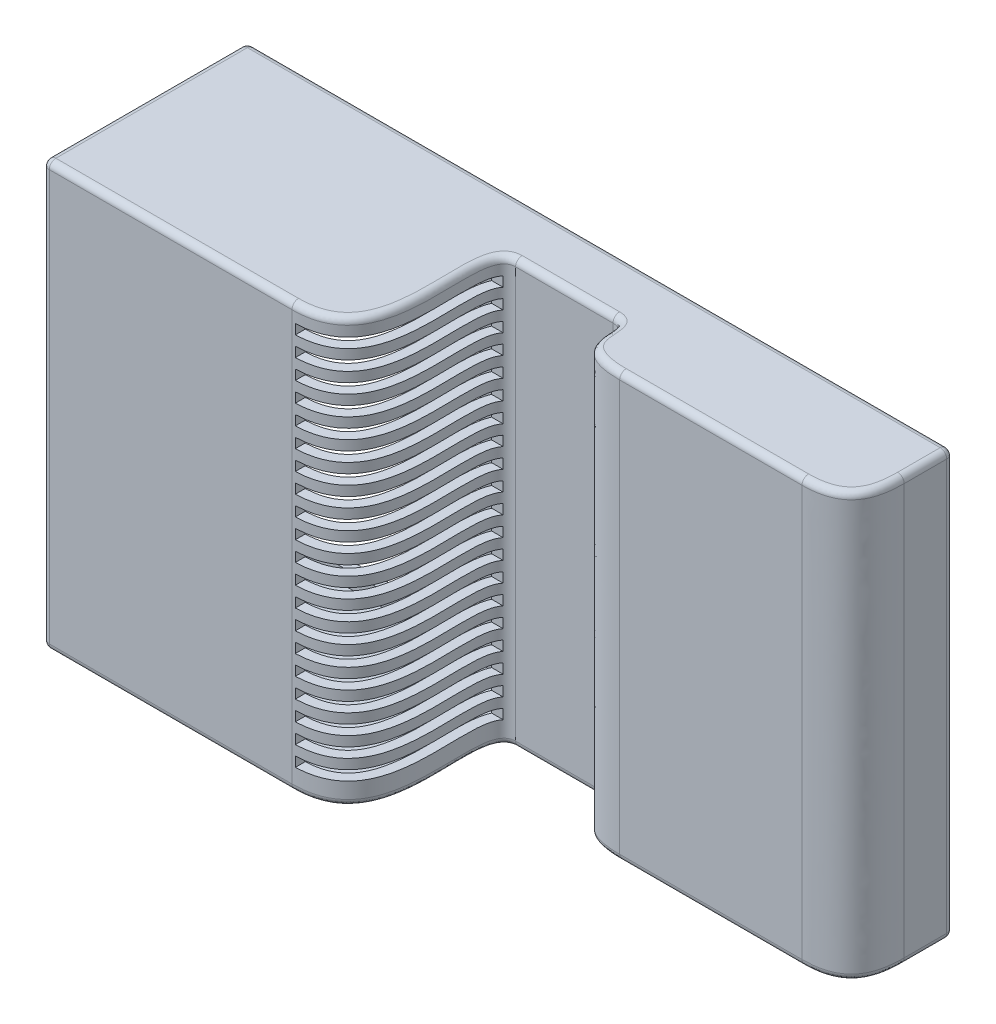
SolidWorks part; units mm, degrees
note: The reader was unsure of these and kept them because the rebuilt part matched: shared geometry of "Sketch1<3>", "Sketch1<4>", "curve_sketch<3>".
ref_plane "Front Plane" through (0, 0, 0) normal (0, 0, 1) x (1, 0, 0)
ref_plane "Top Plane" through (0, 0, 0) normal (0, 1, 0) x (1, 0, 0)
ref_plane "Right Plane" through (0, 0, 0) normal (1, 0, 0) x (0, 0, -1)
sketch "Sketch1" plane through (0, 0, 0) normal (0, 0, 1) x (1, 0, 0)
  line L0 (-14.745, 28.505) -> (-14.745, -28.505)
  line L1 (-13.745, 27.505) -> (13.745, 27.505) construction
  line L2 (-13.745, 27.505) -> (-13.745, -27.505) construction
  line L3 (-13.745, -27.505) -> (13.745, -27.505) construction
  line L4 (13.745, 27.505) -> (13.745, -27.505) construction
  line L5 (-14.745, -28.505) -> (14.745, -28.505)
  line L6 (14.745, 28.505) -> (14.745, -28.505)
  line L7 (-14.745, 28.505) -> (14.745, 28.505)
  line L13 (83.735, 30.745) -> (-20.6993, 30.745)
  line L14 (83.735, 30.745) -> (83.735, -30.755)
  line L15 (83.735, -30.755) -> (-20.6993, -30.755)
  line L16 (-20.6993, 30.745) -> (-20.6993, -30.755)
  line L20 (85.235, 32.245) -> (-22.1993, 32.245)
  line L21 (-22.1993, 32.245) -> (-22.1993, -32.255)
  line L22 (85.235, -32.255) -> (-22.1993, -32.255)
  line L23 (85.235, 32.245) -> (85.235, -32.255)
  line L25 (23.925, 19.36) -> (23.925, -19.36)
  line L26 (24.425, 18.86) -> (76.035, 18.86) construction
  line L27 (24.425, 18.86) -> (24.425, -18.86) construction
  line L28 (24.425, -18.86) -> (76.035, -18.86) construction
  line L29 (76.035, 18.86) -> (76.035, -18.86) construction
  line L30 (23.925, -19.36) -> (76.535, -19.36)
  line L31 (76.535, 19.36) -> (76.535, -19.36)
  line L32 (23.925, 19.36) -> (76.535, 19.36)
  dimension "D3" = 0.5
  dimension "D1" = 1
  dimension "D7" = 1.5
extrude "top" add sketch "Sketch1" against normal blind 1.5 contours L16 L13 L14 L15 L0 L7 L6 L5 | L20 L23 L22 L21 L13 L16 L15 L14
extrude "walls" add sketch "Sketch1<3>" along normal offset from surface (29.6426 mm away) 1 contours L23 L20 L21 L22 L16 L13 L14 L15
sketch "Sketch1<3>" plane through (0, 0, 0) normal (0, 0, 1) x (1, 0, 0) same geometry as "Sketch1"
extrude "bottom" add sketch "Sketch1<4>" against normal blind 1.5 from surface at 29.6426 contours L22 L21 L20 L23 starting at face at (31.5178, -0.005, 29.6426)
sketch "Sketch1<4>" plane through (0, 0, 0) normal (0, 0, 1) x (1, 0, 0) same geometry as "Sketch1"
sketch "curve_sketch" plane through (0, 32.245, 0) normal (0, 1, 0) x (1, 0, 0)
  line L0 (85.235, -29.6426) -> (-22.1993, -29.6426) construction
  line L1 (27.105, -6.9813) -> (41.9297, -6.9813)
  line L2 (49.9345, -13.9679) -> (77.6775, -13.9679)
  line L3 (85.235, 1.5) -> (85.235, -29.6426) construction
  line L4 (-34.1631, -6.9813) -> (-19.6156, -6.9813) construction
  line L5 (-15.8965, -29.6426) -> (-0.5837, -29.6426) construction
  line L6 (-31.7986, -6.9813) -> (-21.9801, -6.9813) construction
  line L7 (-40.8899, -6.9813) -> (-31.9208, -6.9813) construction
  line L8 (-57.8435, -13.9679) -> (-45.1559, -13.9679) construction
  line L9 (-80.5794, -13.9679) -> (-74.7034, -13.9679) construction
  line L10 (85.235, -26.9033) -> (85.235, -27.8055) construction
  line L13 (27.105, -5.4813) -> (41.9297, -5.4813)
  line L14 (49.9345, -12.4679) -> (77.6775, -12.4679)
  line L15 (15.7391, -28.1426) -> (15.7391, -29.6426)
  line L16 (15.7391, -29.6426) -> (85.235, -29.6426)
  line L17 (85.235, -29.6426) -> (85.235, -5.9781)
  line L18 (83.735, -5.9781) -> (85.235, -5.9781)
  spline S0 degree 3 poles (15.7391, -29.6426) (31.0125, -29.6426) (20.9684, -6.9813) (27.105, -6.9813) knots 0 0 0 0 1 1 1 1
  spline S1 degree 3 poles (41.9297, -6.9813) (45.6768, -6.9813) (40.0532, -13.9679) (49.9345, -13.9679) knots 0 0 0 0 1 1 1 1
  spline S2 degree 3 poles (77.6775, -13.9679) (83.9591, -13.9679) (85.235, -10.3756) (85.235, -5.9781) knots 0 0 0 0 1 1 1 1
  spline S3 degree 1 poles (15.7391, -28.1426) (27.105, -5.4813) knots 0 0 1 1 construction
  spline S4 degree 1 poles (41.9297, -5.4813) (49.9345, -12.4679) knots 0 0 1 1 construction
  spline S5 degree 1 poles (77.6775, -12.4679) (83.735, -5.9781) knots 0 0 1 1 construction
  spline S6 degree 3 poles (15.7391, -28.1426) (15.9476, -28.1426) (16.3745, -28.1326) (17.1485, -28.0751) (18.0243, -27.9372) (18.9232, -27.6812) (19.9467, -27.2364) (20.9471, -26.5115) (21.8551, -25.3682) (22.5319, -23.9236) (23.144, -21.6408) (23.4186, -18.2961) (23.3451, -14.812) (23.3131, -12.2028) (23.3664, -10.3819) (23.5747, -8.7266) (23.9827, -7.457) (24.6212, -6.5204) (25.5445, -5.7222) (26.496, -5.4813) (27.105, -5.4813) knots 0 0 0 0 0.015625 0.03125 0.0625 0.09375 0.125 0.1875 0.25 0.3125 0.375 0.5 0.625 0.6875 0.75 0.8125 0.875 0.90625 0.9375 1 1 1 1
  spline S7 degree 3 poles (41.9297, -5.4813) (42.2791, -5.4813) (42.9736, -5.556) (43.9809, -6.0851) (44.6062, -6.943) (44.8568, -7.7451) (44.9576, -8.453) (45.0154, -9.3161) (45.0801, -10.2794) (45.34, -11.0947) (45.7077, -11.5515) (46.3924, -11.9502) (47.1977, -12.2214) (48.1601, -12.3845) (49.1003, -12.4552) (49.6642, -12.4679) (49.9345, -12.4679) knots 0 0 0 0 0.0625 0.125 0.1875 0.25 0.3125 0.375 0.5 0.625 0.75 0.8125 0.875 0.9375 0.96875 1 1 1 1
  spline S8 degree 3 poles (77.6775, -12.4679) (77.8504, -12.4679) (78.2042, -12.4615) (78.8479, -12.4246) (79.5785, -12.3356) (80.3284, -12.1695) (81.1754, -11.882) (81.9728, -11.4236) (82.648, -10.7433) (83.15, -9.8777) (83.5007, -8.7843) (83.6647, -7.6932) (83.7257, -6.7403) (83.735, -6.2294) (83.735, -5.9781) knots 0 0 0 0 0.03125 0.0625 0.125 0.1875 0.25 0.375 0.5 0.625 0.75 0.875 0.9375 1 1 1 1
  line M4 (-22.1993, -29.6426) -> (85.235, -29.6426)
  line M5 (85.235, -29.6426) -> (85.235, 1.5)
  dimension "D1" = 1.5
extrude "curve_cut" cut sketch "curve_sketch" against normal through all contours S2 L2 S1 L1 S0 M4 M5
extrude "curved_wall" add sketch "curve_sketch<3>" against normal up to surface (64.5 mm away) contours S8 L14 S7 L13 S6 L15 S0 L1 S1 L2 S2 L18 up to face at (36.1103, -32.255, 12.8882)
sketch "curve_sketch<3>" plane through (0, 32.245, 0) normal (0, 1, 0) x (1, 0, 0) same geometry as "curve_sketch"
sketch "Sketch2" plane through (85.235, 0, 0) normal (1, 0, 0) x (0, 0, -1)
  line L0 (-31.0953, -24.3247) -> (-7.5397, -24.3247)
  line L5 (-31.0953, -28.8247) -> (-7.5397, -28.8247)
  line L6 (-31.0953, -28.8247) -> (-31.0953, -27.3247)
  line L7 (-31.0953, -27.3247) -> (-7.5397, -27.3247)
  line L8 (-7.5397, -28.8247) -> (-7.5397, -27.3247)
  line L9 (-31.0953, -25.8247) -> (-31.0953, -24.3247)
  line L10 (-31.0953, -25.8247) -> (-7.5397, -25.8247)
  line L11 (-7.5397, -25.8247) -> (-7.5397, -24.3247)
  line L12 (-31.0953, -21.3247) -> (-7.5397, -21.3247)
  line L13 (-31.0953, -22.8247) -> (-31.0953, -21.3247)
  line L14 (-31.0953, -22.8247) -> (-7.5397, -22.8247)
  line L15 (-7.5397, -22.8247) -> (-7.5397, -21.3247)
  line L16 (-31.0953, -18.3247) -> (-7.5397, -18.3247)
  line L17 (-31.0953, -19.8247) -> (-31.0953, -18.3247)
  line L18 (-31.0953, -19.8247) -> (-7.5397, -19.8247)
  line L19 (-7.5397, -19.8247) -> (-7.5397, -18.3247)
  line L20 (-31.0953, -15.3247) -> (-7.5397, -15.3247)
  line L21 (-31.0953, -16.8247) -> (-31.0953, -15.3247)
  line L22 (-31.0953, -16.8247) -> (-7.5397, -16.8247)
  line L23 (-7.5397, -16.8247) -> (-7.5397, -15.3247)
  line L24 (-31.0953, -12.3247) -> (-7.5397, -12.3247)
  line L25 (-31.0953, -13.8247) -> (-31.0953, -12.3247)
  line L26 (-31.0953, -13.8247) -> (-7.5397, -13.8247)
  line L27 (-7.5397, -13.8247) -> (-7.5397, -12.3247)
  line L28 (-31.0953, -9.3247) -> (-7.5397, -9.3247)
  line L29 (-31.0953, -10.8247) -> (-31.0953, -9.3247)
  line L30 (-31.0953, -10.8247) -> (-7.5397, -10.8247)
  line L31 (-7.5397, -10.8247) -> (-7.5397, -9.3247)
  line L32 (-31.0953, -6.3247) -> (-7.5397, -6.3247)
  line L33 (-31.0953, -7.8247) -> (-31.0953, -6.3247)
  line L34 (-31.0953, -7.8247) -> (-7.5397, -7.8247)
  line L35 (-7.5397, -7.8247) -> (-7.5397, -6.3247)
  line L36 (-31.0953, -3.3247) -> (-7.5397, -3.3247)
  line L37 (-31.0953, -4.8247) -> (-31.0953, -3.3247)
  line L38 (-31.0953, -4.8247) -> (-7.5397, -4.8247)
  line L39 (-7.5397, -4.8247) -> (-7.5397, -3.3247)
  line L40 (-31.0953, -0.3247) -> (-7.5397, -0.3247)
  line L41 (-31.0953, -1.8247) -> (-31.0953, -0.3247)
  line L42 (-31.0953, -1.8247) -> (-7.5397, -1.8247)
  line L43 (-7.5397, -1.8247) -> (-7.5397, -0.3247)
  line L44 (-31.0953, 2.6753) -> (-7.5397, 2.6753)
  line L45 (-31.0953, 1.1753) -> (-31.0953, 2.6753)
  line L46 (-31.0953, 1.1753) -> (-7.5397, 1.1753)
  line L47 (-7.5397, 1.1753) -> (-7.5397, 2.6753)
  line L48 (-31.0953, 5.6753) -> (-7.5397, 5.6753)
  line L49 (-31.0953, 4.1753) -> (-31.0953, 5.6753)
  line L50 (-31.0953, 4.1753) -> (-7.5397, 4.1753)
  line L51 (-7.5397, 4.1753) -> (-7.5397, 5.6753)
  line L52 (-31.0953, 8.6753) -> (-7.5397, 8.6753)
  line L53 (-31.0953, 7.1753) -> (-31.0953, 8.6753)
  line L54 (-31.0953, 7.1753) -> (-7.5397, 7.1753)
  line L55 (-7.5397, 7.1753) -> (-7.5397, 8.6753)
  line L56 (-31.0953, 11.6753) -> (-7.5397, 11.6753)
  line L57 (-31.0953, 10.1753) -> (-31.0953, 11.6753)
  line L58 (-31.0953, 10.1753) -> (-7.5397, 10.1753)
  line L59 (-7.5397, 10.1753) -> (-7.5397, 11.6753)
  line L60 (-31.0953, 14.6753) -> (-7.5397, 14.6753)
  line L61 (-31.0953, 13.1753) -> (-31.0953, 14.6753)
  line L62 (-31.0953, 13.1753) -> (-7.5397, 13.1753)
  line L63 (-7.5397, 13.1753) -> (-7.5397, 14.6753)
  line L64 (-31.0953, 17.6753) -> (-7.5397, 17.6753)
  line L65 (-31.0953, 16.1753) -> (-31.0953, 17.6753)
  line L66 (-31.0953, 16.1753) -> (-7.5397, 16.1753)
  line L67 (-7.5397, 16.1753) -> (-7.5397, 17.6753)
  line L68 (-31.0953, 20.6753) -> (-7.5397, 20.6753)
  line L69 (-31.0953, 19.1753) -> (-31.0953, 20.6753)
  line L70 (-31.0953, 19.1753) -> (-7.5397, 19.1753)
  line L71 (-7.5397, 19.1753) -> (-7.5397, 20.6753)
  line L72 (-31.0953, 23.6753) -> (-7.5397, 23.6753)
  line L73 (-31.0953, 22.1753) -> (-31.0953, 23.6753)
  line L74 (-31.0953, 22.1753) -> (-7.5397, 22.1753)
  line L75 (-7.5397, 22.1753) -> (-7.5397, 23.6753)
  line L76 (-31.0953, 26.6753) -> (-7.5397, 26.6753)
  line L77 (-31.0953, 25.1753) -> (-31.0953, 26.6753)
  line L78 (-31.0953, 25.1753) -> (-7.5397, 25.1753)
  line L79 (-7.5397, 25.1753) -> (-7.5397, 26.6753)
  line L80 (-31.0953, 29.6753) -> (-7.5397, 29.6753)
  line L81 (-31.0953, 28.1753) -> (-31.0953, 29.6753)
  line L82 (-31.0953, 28.1753) -> (-7.5397, 28.1753)
  line L83 (-7.5397, 28.1753) -> (-7.5397, 29.6753)
  dimension "D1" = 1.5
  dimension "D2" = 20
extrude "vent_cut" cut sketch "Sketch2" against normal blind 14 from offset 55 offset against normal yes
sketch "buttons_sketch" plane through (0, 30.745, -1.5) normal (0, 0, 1) x (-1, 0, 0)
  line L0 (-85.235, 30.75) -> (22.1993, 30.75) construction
  line L1 (-85.235, -1.5) -> (-85.235, 63) construction
  line L2 (22.1993, -1.5) -> (22.1993, 63) construction
  arc A4 (-27.7936, 58.1856) -> (-27.9934, 58.193) centre (-27.8935, 58.1893) ccw
  arc A5 (-33.1405, 58.3058) -> (-32.941, 58.3207) centre (-33.0407, 58.3132) cw
  arc A6 (-47.7936, 58.1856) -> (-47.9934, 58.193) centre (-47.8935, 58.1893) ccw
  arc A7 (-53.1405, 58.3058) -> (-52.941, 58.3207) centre (-53.0407, 58.3132) cw
  arc A8 (-67.7936, 58.1856) -> (-67.9934, 58.193) centre (-67.8935, 58.1893) ccw
  arc A9 (-73.1405, 58.3058) -> (-72.941, 58.3207) centre (-73.0407, 58.3132) cw
  arc A10 (-73.1405, 3.1942) -> (-72.941, 3.1793) centre (-73.0407, 3.1868) ccw
  arc A11 (-67.7936, 3.3144) -> (-67.9934, 3.307) centre (-67.8935, 3.3107) cw
  arc A12 (-53.1405, 3.1942) -> (-52.941, 3.1793) centre (-53.0407, 3.1868) ccw
  arc A13 (-47.7936, 3.3144) -> (-47.9934, 3.307) centre (-47.8935, 3.3107) cw
  arc A14 (-33.1405, 3.1942) -> (-32.941, 3.1793) centre (-33.0407, 3.1868) ccw
  arc A15 (-27.7936, 3.3144) -> (-27.9934, 3.307) centre (-27.8935, 3.3107) cw
  spline S0 degree 3 poles (-27.7936, 58.1856) (-28.0961, 49.9806) (-32.2754, 46.7301) (-33.1405, 58.3058) knots 0 0 0 0 1 1 1 1
  spline S1 degree 1 poles (-27.9934, 58.193) (-32.941, 58.3207) knots 0 0 1 1 construction
  spline S2 degree 3 poles (-27.9934, 58.193) (-28.0115, 57.7037) (-28.0801, 56.697) (-28.3205, 54.9289) (-28.793, 53.0622) (-29.5445, 51.5364) (-30.2151, 50.9899) (-30.6595, 50.9646) (-31.0184, 51.1303) (-31.4137, 51.5606) (-31.8036, 52.2793) (-32.1668, 53.2977) (-32.4876, 54.6242) (-32.7097, 56.0047) (-32.8534, 57.2629) (-32.9152, 57.9746) (-32.941, 58.3207) knots 0 0 0 0 0.0625 0.125 0.25 0.375 0.5 0.5625 0.625 0.6875 0.75 0.8125 0.875 0.9375 0.96875 1 1 1 1
  spline S3 degree 3 poles (-47.9934, 58.193) (-48.0115, 57.7037) (-48.0801, 56.697) (-48.3205, 54.9289) (-48.793, 53.0622) (-49.5445, 51.5364) (-50.2151, 50.9899) (-50.6595, 50.9646) (-51.0184, 51.1303) (-51.4137, 51.5606) (-51.8036, 52.2793) (-52.1668, 53.2977) (-52.4876, 54.6242) (-52.7097, 56.0047) (-52.8534, 57.2629) (-52.9152, 57.9746) (-52.941, 58.3207) knots 0 0 0 0 0.0625 0.125 0.25 0.375 0.5 0.5625 0.625 0.6875 0.75 0.8125 0.875 0.9375 0.96875 1 1 1 1
  spline S4 degree 3 poles (-47.7936, 58.1856) (-48.0961, 49.9806) (-52.2754, 46.7301) (-53.1405, 58.3058) knots 0 0 0 0 1 1 1 1
  spline S5 degree 3 poles (-67.9934, 58.193) (-68.0115, 57.7037) (-68.0801, 56.697) (-68.3205, 54.9289) (-68.793, 53.0622) (-69.5445, 51.5364) (-70.2151, 50.9899) (-70.6595, 50.9646) (-71.0184, 51.1303) (-71.4137, 51.5606) (-71.8036, 52.2793) (-72.1668, 53.2977) (-72.4876, 54.6242) (-72.7097, 56.0047) (-72.8534, 57.2629) (-72.9152, 57.9746) (-72.941, 58.3207) knots 0 0 0 0 0.0625 0.125 0.25 0.375 0.5 0.5625 0.625 0.6875 0.75 0.8125 0.875 0.9375 0.96875 1 1 1 1
  spline S6 degree 3 poles (-67.7936, 58.1856) (-68.0961, 49.9806) (-72.2754, 46.7301) (-73.1405, 58.3058) knots 0 0 0 0 1 1 1 1
  spline S7 degree 3 poles (-67.7936, 3.3144) (-68.0961, 11.5194) (-72.2754, 14.7699) (-73.1405, 3.1942) knots 0 0 0 0 1 1 1 1
  spline S8 degree 3 poles (-67.9934, 3.307) (-68.0115, 3.7963) (-68.0801, 4.803) (-68.3205, 6.5711) (-68.793, 8.4378) (-69.5445, 9.9636) (-70.2151, 10.5101) (-70.6595, 10.5354) (-71.0184, 10.3697) (-71.4137, 9.9394) (-71.8036, 9.2207) (-72.1668, 8.2023) (-72.4876, 6.8758) (-72.7097, 5.4953) (-72.8534, 4.2371) (-72.9152, 3.5254) (-72.941, 3.1793) knots 0 0 0 0 0.0625 0.125 0.25 0.375 0.5 0.5625 0.625 0.6875 0.75 0.8125 0.875 0.9375 0.96875 1 1 1 1
  spline S9 degree 3 poles (-47.7936, 3.3144) (-48.0961, 11.5194) (-52.2754, 14.7699) (-53.1405, 3.1942) knots 0 0 0 0 1 1 1 1
  spline S10 degree 3 poles (-47.9934, 3.307) (-48.0115, 3.7963) (-48.0801, 4.803) (-48.3205, 6.5711) (-48.793, 8.4378) (-49.5445, 9.9636) (-50.2151, 10.5101) (-50.6595, 10.5354) (-51.0184, 10.3697) (-51.4137, 9.9394) (-51.8036, 9.2207) (-52.1668, 8.2023) (-52.4876, 6.8758) (-52.7097, 5.4953) (-52.8534, 4.2371) (-52.9152, 3.5254) (-52.941, 3.1793) knots 0 0 0 0 0.0625 0.125 0.25 0.375 0.5 0.5625 0.625 0.6875 0.75 0.8125 0.875 0.9375 0.96875 1 1 1 1
  spline S11 degree 3 poles (-27.9934, 3.307) (-28.0115, 3.7963) (-28.0801, 4.803) (-28.3205, 6.5711) (-28.793, 8.4378) (-29.5445, 9.9636) (-30.2151, 10.5101) (-30.6595, 10.5354) (-31.0184, 10.3697) (-31.4137, 9.9394) (-31.8036, 9.2207) (-32.1668, 8.2023) (-32.4876, 6.8758) (-32.7097, 5.4953) (-32.8534, 4.2371) (-32.9152, 3.5254) (-32.941, 3.1793) knots 0 0 0 0 0.0625 0.125 0.25 0.375 0.5 0.5625 0.625 0.6875 0.75 0.8125 0.875 0.9375 0.96875 1 1 1 1
  spline S12 degree 3 poles (-27.7936, 3.3144) (-28.0961, 11.5194) (-32.2754, 14.7699) (-33.1405, 3.1942) knots 0 0 0 0 1 1 1 1
  dimension "D1" = 0.2
  dimension "D2" = 2
  dimension "D3" = 3
extrude "buttons_cut" cut sketch "buttons_sketch" along normal up to next
fillet "Fillet1" radius 1 21 edges at (34.5173, -32.255, 6.9813) (63.806, -32.255, 13.9679) (85.235, -32.255, 2.2391) (31.5178, -32.255, -1.5) (-22.1993, -32.255, 14.0713) (-3.2301, -32.255, 29.6426) (-22.1993, 32.245, 14.0713) (31.5178, 32.245, -1.5) (85.235, 32.245, 2.2391) (63.806, 32.245, 13.9679) (34.5173, 32.245, 6.9813) (-3.2301, 32.245, 29.6426) (-22.1993, -0.005, 29.6426) (-22.1993, -0.005, -1.5) (85.235, -0.005, -1.5)
